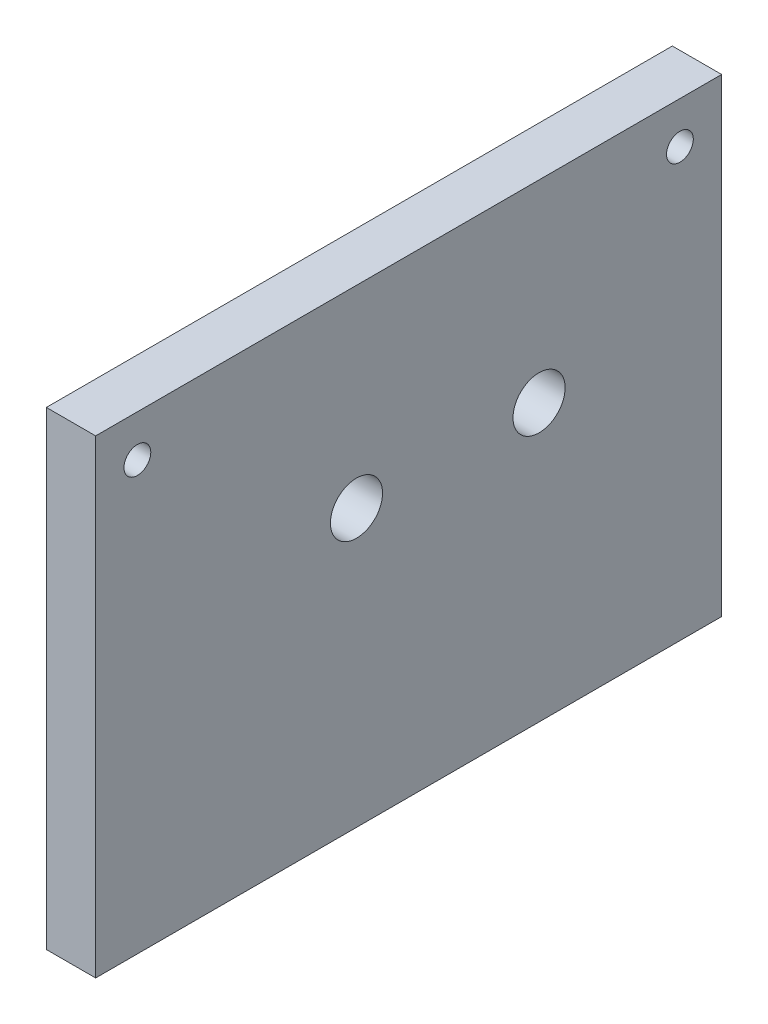
SolidWorks part; units mm, degrees
ref_plane "Front Plane" through (0, 0, 0) normal (0, 0, 1) x (1, 0, 0)
ref_plane "Top Plane" through (0, 0, 0) normal (0, 1, 0) x (1, 0, 0)
ref_plane "Right Plane" through (0, 0, 0) normal (1, 0, 0) x (0, 0, -1)
sketch "Sketch1" plane through (0, 0, 0) normal (1, 0, 0) x (0, 0, -1)
  line L0 (-66.04, 46.99) -> (66.04, 46.99) construction
  line L1 (-76.2, 57.15) -> (76.2, 57.15)
  line L2 (-76.2, 57.15) -> (-76.2, -57.15)
  line L3 (-76.2, -57.15) -> (76.2, -57.15)
  line L4 (76.2, 57.15) -> (76.2, -57.15)
  line L5 (-76.2, 57.15) -> (76.2, -57.15) construction
  line L6 (-76.2, -57.15) -> (76.2, 57.15) construction
  line L7 (-76.2, -54.04) -> (76.2, -54.04) construction
  line L8 (-76.2, -54.04) -> (-76.2, -66.04) construction
  line L9 (-76.2, -66.04) -> (76.2, -66.04) construction
  line L10 (76.2, -54.04) -> (76.2, -66.04) construction
  circle A2 centre (-12.7, 10.16) radius 6.3436
  circle A3 centre (-12.7, 10.16) radius 32.8422 construction
  circle A4 centre (31.75, 10.16) radius 6.3437
  circle A5 centre (31.75, 10.16) radius 32.8422 construction
  circle A6 centre (-12.7, 10.16) radius 13.7287 construction
  circle A7 centre (31.75, 10.16) radius 13.7287 construction
  point P0 (0, 0)
  point P20 (0, 46.99)
  point P21 (0, 0)
  dimension "D4" = 76.2
  dimension "D5" = 65.6844
  dimension "D8" = 27.4574
  dimension "D9" = 12.6873
  dimension "D11" = 10.16
  dimension "D1" = 152.4
  dimension "D2" = 114.3
  dimension "D3" = 12
  dimension "D6" = 67.31
  dimension "D7" = 44.45
  dimension "D10" = 63.5
  dimension "D12" = 10.16
extrude "Boss-Extrude1" add sketch "Sketch1" along normal blind 12
sketch "Sketch2" plane through (0, -57.15, 0) normal (0, -1, 0) x (1, 0, 0)
  line L0 (6, -66.675) -> (6, 66.675) construction
  line L1 (12, 76.2) -> (0, 76.2) construction
  line L2 (12, -76.2) -> (0, -76.2) construction
  point P2 (0, 0)
  point P4 (6, 0)
  point P9 (6, -76.2)
  point P10 (0, 0)
  point P11 (57.9749, 66.675)
  point P14 (0, 0)
  dimension "D1" = 9.525
hole_wizard "Tap Drill for #10-32 Tap1" positions "Sketch3" profile "Sketch4" hole size "#10-32" standard "ANSI Inch"
sketch "Sketch3" plane through (0, -57.15, 0) normal (0, -1, 0) x (-1, 0, 0)
  point P0 (-6, -66.675)
  point P3 (-6, 0)
  point P6 (-6, 66.675)
sketch "Sketch4" plane through (6, -57.15, 66.675) normal (1, 0, 0) x (0, 0, -1)
  line L0 (0, 0) -> (0, 13.9133)
  line L1 (0, 13.9133) -> (2.0193, 12.7)
  line L2 (2.0193, 12.7) -> (2.0193, 0)
  line L5 (2.0193, 0) -> (0, 0)
  line L10 (0, 13.9133) -> (-2.0193, 12.7) construction
  line L11 (0, -6.35) -> (0, 107.95) construction
  dimension "Hole Dia." = 4.0386
  dimension "Hole Depth" = 12.7
  dimension "Drill Angle" = 118
hole_wizard "1/4 Clearance Hole1" positions "Sketch5" profile "Sketch6" hole size "1/4" standard "ANSI Inch"
sketch "Sketch5" plane through (0, 0, 0) normal (-1, 0, 0) x (0, 0, 1)
  point P0 (-66.04, 46.99)
  point P3 (66.04, 46.99)
sketch "Sketch6" plane through (0, 46.99, -66.04) normal (0, 1, 0) x (0, 0, 1)
  line L0 (0, 0) -> (0, 14.6611)
  line L1 (0, 14.6611) -> (3.2639, 12.7)
  line L2 (3.2639, 12.7) -> (3.2639, 0)
  line L5 (3.2639, 0) -> (0, 0)
  line L10 (0, 14.6611) -> (-3.2639, 12.7) construction
  line L11 (0, -6.35) -> (0, 107.95) construction
  dimension "Hole Dia." = 6.5278
  dimension "Hole Depth" = 12.7
  dimension "Drill Angle" = 118
